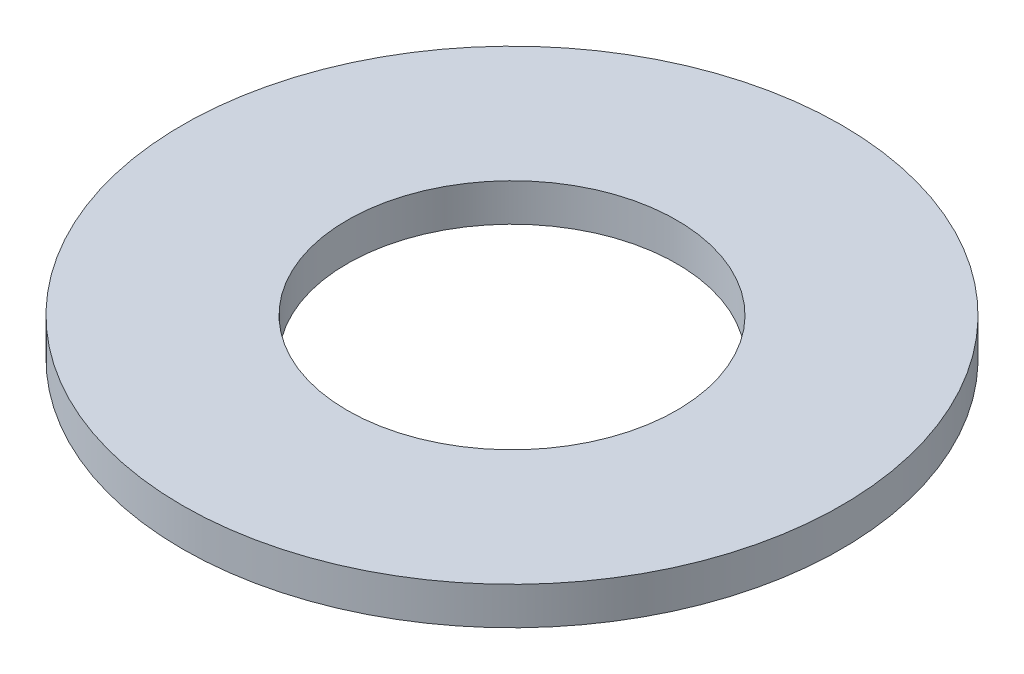
SolidWorks part; units mm, degrees
ref_plane "Front Plane" through (0, 0, 0) normal (0, 0, 1) x (1, 0, 0)
ref_plane "Top Plane" through (0, 0, 0) normal (0, 1, 0) x (1, 0, 0)
ref_plane "Right Plane" through (0, 0, 0) normal (1, 0, 0) x (0, 0, -1)
sketch "Sketch1" plane through (0, 0, 0) normal (0, 1, 0) x (1, 0, 0)
  circle A0 centre (0, 0) radius 35
  dimension "FLANGE_OD" = 70
extrude "Boss-Extrude1" add sketch "Sketch1" along normal blind 4
sketch "Sketch2" plane through (0, 0, 0) normal (0, 1, 0) x (1, 0, 0)
  circle A0 centre (0, 0) radius 17.5
  dimension "BORE_D" = 35
extrude "Cut-Extrude1" cut sketch "Sketch2" along normal through all
sketch "Sketch3" plane through (0, 4, 0) normal (0, 1, 0) x (1, 0, 0)
  circle A0 centre (0, 0) radius 13.711 construction
  circle A1 centre (-13.711, 0) radius 3.0843
  dimension "BOLT_D" = 6.1685
  dimension "BOLT_PCD" = 27.4219
extrude "Cut-Extrude2" cut sketch "Sketch3" against normal blind 3.8606 rebuild error yes
pattern_circular "CirPattern1" count 3 over 360 rebuild error yes
